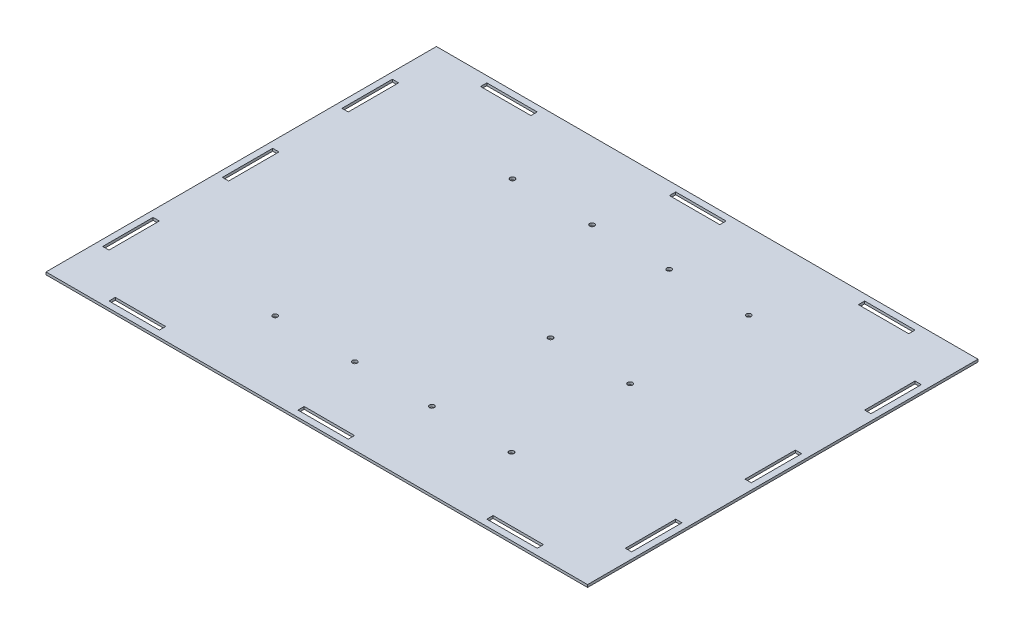
SolidWorks part; units mm, degrees
ref_plane "Front Plane" through (0, 0, 0) normal (0, 0, 1) x (1, 0, 0)
ref_plane "Top Plane" through (0, 0, 0) normal (0, 1, 0) x (1, 0, 0)
ref_plane "Right Plane" through (0, 0, 0) normal (1, 0, 0) x (0, 0, -1)
sketch "Sketch1" plane through (0, 0, 0) normal (0, 1, 0) x (1, 0, 0)
  line L0 (0, 63.5) -> (0, -63.5)
  line L1 (-273.05, 63.5) -> (273.05, 63.5)
  line L2 (-273.05, 63.5) -> (-273.05, -63.5)
  line L4 (273.05, 63.5) -> (273.05, -63.5)
  line L5 (-273.05, -63.5) -> (-273.05, -133.35)
  line L6 (-273.05, -133.35) -> (273.05, -133.35)
  line L7 (273.05, -133.35) -> (273.05, -63.5)
  dimension "D2" = 127
extrude "Boss-Extrude1" add sketch "Sketch1" along normal blind 2.54 contours L2 L0 L1 | L4 L1 L0 region at (-136.525, 0, -57.695)
hole_wizard "#11 (0.191) Diameter Hole2" positions "Sketch10" profile "Sketch9" hole size "#11" standard "ANSI Inch" end condition through all
sketch "Sketch10" plane through (0, 2.54, 0) normal (0, 1, 0) x (1, 0, 0)
  line L0 (-273.05, 63.5) -> (-273.05, -133.35) construction
  line L1 (273.05, 63.5) -> (273.05, -133.35) construction
  point P0 (-119.126, -56.1278)
  point P2 (-38.862, -56.1278)
  point P4 (38.862, -56.1278)
  point P6 (119.126, -56.1278)
  dimension "D1" = 153.924
  dimension "D2" = 153.924
  dimension "D3" = 80.264
  dimension "D4" = 80.264
sketch "Sketch9" plane through (-119.126, 2.54, 56.1278) normal (1, 0, 0) x (0, 0, 1)
  line L0 (0, 0) -> (0, 2.54)
  line L1 (0, 2.54) -> (2.4257, 2.54)
  line L2 (2.4257, 2.54) -> (2.4257, 0)
  line L5 (2.4257, 0) -> (0, 0)
  line L11 (0, -6.35) -> (0, 107.95) construction
  dimension "Thru Hole Dia." = 4.8514
  dimension "Thru Hole Depth" = 2.54
hole_wizard "#11 (0.191) Diameter Hole3" positions "Sketch14" profile "Sketch13" hole size "#11" standard "ANSI Inch" end condition through all
sketch "Sketch14" plane through (0, 2.54, 0) normal (0, 1, 0) x (1, 0, 0)
  point P0 (119.126, 63.5)
  point P2 (38.862, 63.5)
sketch "Sketch13" plane through (119.126, 2.54, -63.5) normal (1, 0, 0) x (0, 0, 1)
  line L0 (0, 0) -> (0, 2.54)
  line L1 (0, 2.54) -> (2.4257, 2.54)
  line L2 (2.4257, 2.54) -> (2.4257, 0)
  line L5 (2.4257, 0) -> (0, 0)
  line L11 (0, -6.35) -> (0, 107.95) construction
  dimension "Thru Hole Dia." = 4.8514
  dimension "Thru Hole Depth" = 2.54
sketch "Sketch17" plane through (0, 2.54, 0) normal (0, 1, 0) x (1, 0, 0)
  line L0 (-273.05, -133.35) -> (-273.05, -63.5) construction
  line L1 (-266.7, -31.75) -> (-260.35, -31.75)
  line L2 (-266.7, -31.75) -> (-266.7, -82.55)
  line L3 (-266.7, -82.55) -> (-260.35, -82.55)
  line L4 (-260.35, -31.75) -> (-260.35, -82.55)
  line L5 (-273.05, -133.35) -> (273.05, -133.35) construction
  line L6 (-215.9, -127) -> (-165.1, -127)
  line L7 (-215.9, -127) -> (-215.9, -120.65)
  line L8 (-215.9, -120.65) -> (-165.1, -120.65)
  line L9 (-165.1, -127) -> (-165.1, -120.65)
  line L10 (273.05, 63.5) -> (273.05, -133.35) construction
  line L11 (165.1, -120.65) -> (215.9, -120.65)
  line L12 (165.1, -120.65) -> (165.1, -127)
  line L13 (165.1, -127) -> (215.9, -127)
  line L14 (215.9, -120.65) -> (215.9, -127)
  line L15 (260.35, -31.75) -> (266.7, -31.75)
  line L16 (260.35, -31.75) -> (260.35, -82.55)
  line L17 (260.35, -82.55) -> (266.7, -82.55)
  line L18 (266.7, -31.75) -> (266.7, -82.55)
  line L19 (-273.05, 63.5) -> (36.4363, 63.5) construction
  line L20 (-25.4, -120.65) -> (25.4, -120.65)
  line L21 (-25.4, -120.65) -> (-25.4, -127)
  line L22 (-25.4, -127) -> (25.4, -127)
  line L23 (25.4, -120.65) -> (25.4, -127)
  line L24 (-266.7, 63.5) -> (-260.35, 63.5)
  line L25 (-266.7, 63.5) -> (-266.7, 38.1)
  line L26 (-266.7, 38.1) -> (-260.35, 38.1)
  line L27 (-260.35, 63.5) -> (-260.35, 38.1)
  line L28 (-273.05, 63.5) -> (-273.05, -133.35) construction
  line L29 (121.5517, 63.5) -> (273.05, 63.5) construction
  line L30 (266.7, 63.5) -> (260.35, 63.5)
  line L31 (266.7, 63.5) -> (266.7, 38.1)
  line L32 (266.7, 38.1) -> (260.35, 38.1)
  line L33 (260.35, 63.5) -> (260.35, 38.1)
  dimension "D1" = 6.35
  dimension "D2" = 6.35
  dimension "D3" = 50.8
  dimension "D4" = 6.35
  dimension "D5" = 50.8
  dimension "D6" = 6.35
  dimension "D7" = 50.8
  dimension "D8" = 50.8
  dimension "D9" = 6.35
  dimension "D10" = 6.35
  dimension "D11" = 50.8
  dimension "D12" = 50.8
  dimension "D13" = 6.35
  dimension "D14" = 6.35
  dimension "D15" = 50.8
  dimension "D16" = 50.8
  dimension "D17" = 50.8
  dimension "D18" = 6.35
  dimension "D19" = 6.35
  dimension "D20" = 139.7
  dimension "D21" = 139.7
  dimension "D22" = 6.35
  dimension "D23" = 6.35
  dimension "D24" = 25.4
  dimension "D25" = 6.35
  dimension "D26" = 6.35
  dimension "D27" = 25.4
extrude "Cut-Extrude12" cut sketch "Sketch17" against normal through all
mirror "Mirror1" about plane through (0, 2.54, -63.5) normal (0, 0, -1) of "Cut-Extrude12", "#11 (0.191) Diameter Hole3", "#11 (0.191) Diameter Hole2", "Boss-Extrude1"
shell "Shell1" thickness 0.1016
